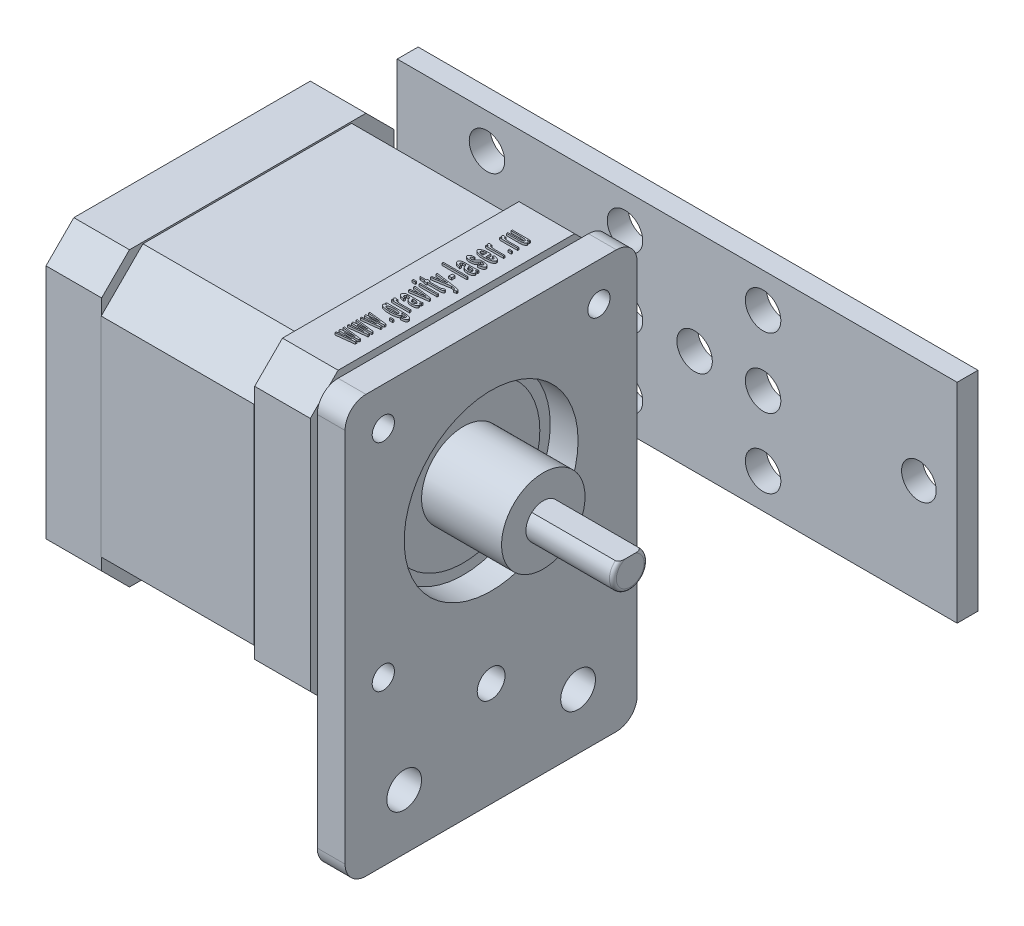
SolidWorks part; units mm, degrees
ref_plane "Спереди" through (0, 0, 0) normal (0, 0, 1) x (1, 0, 0)
ref_plane "Сверху" through (0, 0, 0) normal (0, 1, 0) x (1, 0, 0)
ref_plane "Справа" through (0, 0, 0) normal (1, 0, 0) x (0, 0, -1)
ref_plane "Плоскость1" through (0, 0, 0) normal (1, 0, 0) x (0, 0, -1)
sketch "Эскиз1" plane through (0, 0, 0) normal (1, 0, 0) x (0, 0, -1)
  line L0 (21, 60) -> (21, 39) construction
  line L1 (3, 0) -> (39, 0)
  line L2 (0, 3) -> (0, 57)
  line L3 (3, 60) -> (39, 60)
  line L4 (42, 3) -> (42, 57)
  line L5 (21, 39) -> (21, 54.5) construction
  line L6 (21, 39) -> (21, 23.5) construction
  line L7 (21, 23.5) -> (5.5, 23.5) construction
  line L8 (5.5, 23.5) -> (5.5, 54.5) construction
  line L9 (5.5, 54.5) -> (21, 54.5) construction
  line L10 (21, 0) -> (21, 8) construction
  line L11 (21, 8) -> (8.5, 8) construction
  line L12 (8.5, 8) -> (33.5, 8) construction
  circle A0 centre (21, 39) radius 12.5
  circle A1 centre (5.5, 54.5) radius 1.6
  circle A2 centre (5.5, 23.5) radius 1.6
  circle A3 centre (36.5, 23.5) radius 1.6
  circle A4 centre (36.5, 54.5) radius 1.6
  circle A5 centre (8.5, 8) radius 2.5
  circle A6 centre (33.5, 8) radius 2.5
  arc A7 (0, 57) -> (3, 60) centre (3, 57) cw
  arc A8 (0, 3) -> (3, 0) centre (3, 3) ccw
  arc A9 (39, 0) -> (42, 3) centre (39, 3) ccw
  arc A10 (42, 57) -> (39, 60) centre (39, 57) ccw
  point P28 (0, 0)
  point P31 (42, 0)
  point P34 (42, 60)
  dimension "D3" = 25
  dimension "D8" = 3.2
  dimension "D9" = 3.2
  dimension "D11" = 5
  dimension "D13" = 3
  dimension "D1" = 42
  dimension "D2" = 60
  dimension "D4" = 21
  dimension "D5" = 15.5
  dimension "D6" = 15.5
  dimension "D7" = 31
  dimension "D10" = 8
  dimension "D12" = 12.5
extrude "Бобышка-Вытянуть1" add sketch "Эскиз1" along normal blind 4
ref_plane "Плоскость2" through (0, 0, -80) normal (0, 0, 1) x (1, 0, 0)
sketch "Эскиз2" plane through (0, 0, -80) normal (0, 0, 1) x (1, 0, 0)
  line L0 (-32.75, 15) -> (-32.75, 30) construction
  line L1 (0, 30) -> (-65.5, 30)
  line L2 (-32.75, 15) -> (-32.75, 0) construction
  line L3 (-65.5, 30) -> (-65.5, 0)
  line L4 (-65.5, 0) -> (0, 0)
  line L5 (0, 30) -> (0, 0)
  circle A0 centre (-22.75, 15) radius 2.55
  circle A1 centre (-12.9, 5) radius 2.55
  circle A2 centre (-12.9, 15) radius 2.55
  circle A3 centre (-12.9, 25) radius 2.55
  circle A4 centre (-42.75, 15) radius 2.55
  circle A5 centre (-52.6, 15) radius 2.55
  circle A6 centre (-52.6, 25) radius 2.55
  circle A7 centre (-52.6, 5) radius 2.55
  circle A8 centre (-32.75, 15) radius 2.55
  circle A9 centre (-32.75, 25) radius 2.55
  circle A10 centre (-32.75, 5) radius 2.55
  dimension "D1" = 5.1
  dimension "D2" = 5.1
  dimension "D3" = 5.1
  dimension "D7" = 5.1
  dimension "D4" = 15
  dimension "D5" = 15
  dimension "D6" = 32.75
extrude "Бобышка-Вытянуть2" add sketch "Эскиз2" along normal blind 3 separate body
sketch "Эскиз3" plane through (0, 0, -80) normal (0, 0, 1) x (1, 0, 0)
  line L1 (0, 0) -> (15, 0)
  line L2 (0, 0) -> (0, 30)
  line L3 (0, 30) -> (15, 30)
  line L4 (15, 0) -> (15, 30)
  dimension "D1" = 15
  dimension "D2" = 30
extrude "Бобышка-Вытянуть3" add sketch "Эскиз3" along normal blind 3
ref_plane "Плоскость3" through (0, 0, -80) normal (0, 0, -1) x (-1, 0, 0)
sketch "Эскиз4" plane through (0, 0, -80) normal (0, 0, -1) x (-1, 0, 0)
  line L0 (-15, 30) -> (-4, 30) construction
  line L1 (-4, 3) -> (-4, 57) construction
  line L2 (-4, 30) -> (-9.5, 30) construction
  line L3 (-9.5, 30) -> (-9.5, 0) construction
  line L4 (65.5, 0) -> (-15, 0) construction
  circle A0 centre (-9.5, 15) radius 2.4923
  dimension "D1" = 4.9846
extrude "Вырез-Вытянуть1" cut sketch "Эскиз4" against normal blind 10
ref_plane "Плоскость4" through (4, 0, 0) normal (1, 0, 0) x (0, 0, -1)
sketch "Эскиз5" plane through (4, 0, 0) normal (1, 0, 0) x (0, 0, -1)
  line L0 (0, 0) -> (42, 0) construction
  line L1 (42, 0) -> (21, 0) construction
  line L2 (21, 0) -> (21, 15) construction
  circle A0 centre (21, 15) radius 2
  dimension "D1" = 4
extrude "Вырез-Вытянуть2" cut sketch "Эскиз5" against normal blind 10 and the other way blind 10
ref_plane "Плоскость5" through (-1, 0, 0) normal (-1, 0, 0) x (0, 0, 1)
sketch "Эскиз6" plane through (-1, 0, 0) normal (-1, 0, 0) x (0, 0, 1)
  line L0 (-42, 60) -> (-38, 60) construction
  line L1 (-42, 60) -> (0, 60) construction
  line L2 (-42, 60) -> (-42, 18) construction
  line L3 (-42, 18) -> (0, 18) construction
  line L4 (0, 60) -> (0, 18) construction
  line L5 (-42, 60) -> (0, 18) construction
  line L6 (-42, 18) -> (0, 60) construction
  line L7 (-42, 60) -> (-42, 56) construction
  line L8 (-42, 56) -> (-38, 60)
  line L9 (-21, 39) -> (-42, 39) construction
  line L10 (-21, 39) -> (-21, 60) construction
  line L11 (0, 56) -> (-4, 60)
  line L12 (0, 22) -> (-4, 18)
  line L13 (-42, 22) -> (-38, 18)
  line L14 (-38, 60) -> (-4, 60)
  line L15 (0, 56) -> (0, 22)
  line L16 (-4, 18) -> (-38, 18)
  line L17 (-42, 22) -> (-42, 56)
  point P0 (-21, 39)
  dimension "D1" = 42
  dimension "D2" = 42
  dimension "D3" = 4
  dimension "D4" = 4
extrude "Бобышка-Вытянуть4" add sketch "Эскиз6" along normal blind 8 separate body
ref_plane "Плоскость6" through (-9, 0, 0) normal (-1, 0, 0) x (0, 0, 1)
sketch "Эскиз7" plane through (-9, 0, 0) normal (-1, 0, 0) x (0, 0, 1)
  line L0 (-41.9404, 59.7724) -> (-35.9404, 59.7724) construction
  line L1 (-41.9404, 59.7724) -> (0.0596, 59.7724) construction
  line L2 (-41.9404, 59.7724) -> (-41.9404, 17.7724) construction
  line L3 (-41.9404, 17.7724) -> (0.0596, 17.7724) construction
  line L4 (0.0596, 59.7724) -> (0.0596, 17.7724) construction
  line L5 (-41.9404, 59.7724) -> (0.0596, 17.7724) construction
  line L6 (-41.9404, 17.7724) -> (0.0596, 59.7724) construction
  line L7 (-41.9404, 59.7724) -> (-41.9404, 53.7724) construction
  line L8 (-41.9404, 53.7724) -> (-35.9404, 59.7724)
  line L9 (-20.9404, 38.7724) -> (-41.9404, 38.7724) construction
  line L10 (-20.9404, 38.7724) -> (-20.9404, 59.7724) construction
  line L11 (0.0596, 53.7724) -> (-5.9404, 59.7724)
  line L12 (0.0596, 23.7724) -> (-5.9404, 17.7724)
  line L13 (-41.9404, 23.7724) -> (-35.9404, 17.7724)
  line L14 (-35.9404, 59.7724) -> (-5.9404, 59.7724)
  line L15 (0.0596, 53.7724) -> (0.0596, 23.7724)
  line L16 (-5.9404, 17.7724) -> (-35.9404, 17.7724)
  line L17 (-41.9404, 23.7724) -> (-41.9404, 53.7724)
  point P0 (-20.9404, 38.7724)
  dimension "D1" = 42
  dimension "D2" = 42
  dimension "D3" = 6
  dimension "D4" = 6
extrude "Бобышка-Вытянуть5" add sketch "Эскиз7" along normal blind 22
ref_plane "Плоскость7" through (-31, 0, 0) normal (-1, 0, 0) x (0, 0, 1)
sketch "Эскиз8" plane through (-31, 0, 0) normal (-1, 0, 0) x (0, 0, 1)
  line L0 (-42, 60) -> (-38, 60) construction
  line L1 (-42, 60) -> (0, 60) construction
  line L2 (-42, 60) -> (-42, 18) construction
  line L3 (-42, 18) -> (0, 18) construction
  line L4 (0, 60) -> (0, 18) construction
  line L5 (-42, 60) -> (0, 18) construction
  line L6 (-42, 18) -> (0, 60) construction
  line L7 (-42, 60) -> (-42, 56) construction
  line L8 (-42, 56) -> (-38, 60)
  line L9 (-21, 39) -> (-42, 39) construction
  line L10 (-21, 39) -> (-21, 60) construction
  line L11 (0, 56) -> (-4, 60)
  line L12 (0, 22) -> (-4, 18)
  line L13 (-42, 22) -> (-38, 18)
  line L14 (-38, 60) -> (-4, 60)
  line L15 (0, 56) -> (0, 22)
  line L16 (-4, 18) -> (-38, 18)
  line L17 (-42, 22) -> (-42, 56)
  point P0 (-21, 39)
  dimension "D1" = 42
  dimension "D2" = 42
  dimension "D3" = 4
  dimension "D4" = 4
extrude "Бобышка-Вытянуть6" add sketch "Эскиз8" along normal blind 8
ref_plane "Плоскость8" through (-39, 0, 0) normal (-1, 0, 0) x (0, 0, 1)
sketch "Эскиз9" plane through (-39, 0, 0) normal (-1, 0, 0) x (0, 0, 1)
  circle A0 centre (-21, 39) radius 4.5
  dimension "D1" = 9
extrude "Вырез-Вытянуть3" cut sketch "Эскиз9" against normal blind 88
ref_plane "Плоскость9" through (-1, 0, 0) normal (1, 0, 0) x (0, 0, -1)
sketch "Эскиз10" plane through (-1, 0, 0) normal (1, 0, 0) x (0, 0, -1)
  circle A0 centre (21, 39) radius 12.25
  circle A1 centre (21, 39) radius 4.5
  dimension "D1" = 24.5
  dimension "D2" = 9
extrude "Бобышка-Вытянуть7" add sketch "Эскиз10" along normal blind 1
ref_plane "Плоскость10" through (-35, 0, 0) normal (1, 0, 0) x (0, 0, -1)
sketch "Эскиз11" plane through (-35, 0, 0) normal (1, 0, 0) x (0, 0, -1)
  circle A0 centre (21, 39) radius 4
  circle A1 centre (21, 39) radius 2.5
  dimension "D1" = 8
  dimension "D2" = 5
extrude "Бобышка-Вытянуть8" add sketch "Эскиз11" along normal blind 30 separate body
ref_plane "Плоскость11" through (-35, 0, 0) normal (1, 0, 0) x (0, 0, -1)
sketch "Эскиз12" plane through (-35, 0, 0) normal (1, 0, 0) x (0, 0, -1)
  circle A0 centre (21, 39) radius 2.495
  dimension "D1" = 4.99
extrude "Бобышка-Вытянуть9" add sketch "Эскиз12" along normal blind 59 separate body
ref_plane "Плоскость12" through (0, 0, -21) normal (0, 0, 1) x (1, 0, 0)
sketch "Эскиз14" plane through (0, 0, -21) normal (0, 0, 1) x (1, 0, 0)
  line L0 (24, 41.495) -> (24, 36.505) construction
  line L1 (24, 36.505) -> (24, 39) construction
  line L2 (24, 39) -> (24, 41.495) construction
  line L3 (24, 41.495) -> (24, 39) construction
  line L4 (24, 39) -> (24, 40.2475) construction
  line L5 (24, 40.2475) -> (24, 41.495) construction
  line L6 (24, 41.495) -> (24, 40.8713) construction
  line L7 (24, 40.8713) -> (9, 40.8713) construction
  line L9 (9, 40.8713) -> (25.6583, 40.8713)
  line L10 (9, 40.8713) -> (9, 46.1963)
  line L11 (9, 46.1963) -> (25.6583, 46.1963)
  line L12 (25.6583, 40.8713) -> (25.6583, 46.1963)
  dimension "D1" = 15
fillet "Скругление1" radius 0.5 1 edges at (24, 39, -23.495) type face fillet first side face at (24, 39, -23.495) second side face at (24, 39, -23.495)
extrude "Вырез-Вытянуть4" cut sketch "Эскиз14" against normal blind 55 and the other way blind 55
extrude "Вырез-Вытянуть5" cut sketch "Эскиз1<3>" against normal blind 5 contours A1 | A4 | A3 | A2
sketch "Эскиз1<3>" plane through (0, 0, 0) normal (1, 0, 0) x (0, 0, -1) same geometry as "Эскиз1"
ref_plane "Плоскость13" through (0, 60, 0) normal (0, 1, 0) x (1, 0, 0)
sketch "Эскиз15" plane through (0, 60, 0) normal (0, 1, 0) x (1, 0, 0)
  line L0 (-9, 4) -> (-1, 4) construction
  line L1 (-1, 4) -> (-5, 4) construction
  line L2 (-5, 4) -> (-3, 4) construction
  line L3 (-3, 4) -> (-3, 38) construction
  line L4 (-9, 38) -> (-1, 38) construction
  text T0 "www.gravity-laser.ru" font "Arial" height in points 14
extrude "Бобышка-Вытянуть10" add sketch "Эскиз15" along normal blind 0.3 and the other way blind 1
other "Move Face1" flip direction yes face at (0, 39, -33.25) offset 1.25 parameters "D1"=1.25
sketch "Sketch1" plane through (0, 0, 0) normal (1, 0, 0) x (0, 0, -1)
  circle A0 centre (21, 39) radius 6
  circle A1 centre (21, 39) radius 2.5 construction
  circle A2 centre (21, 39) radius 2.5
  dimension "D1" = 12
extrude "Boss-Extrude1" add sketch "Sketch1" along normal blind 11.5 separate body
